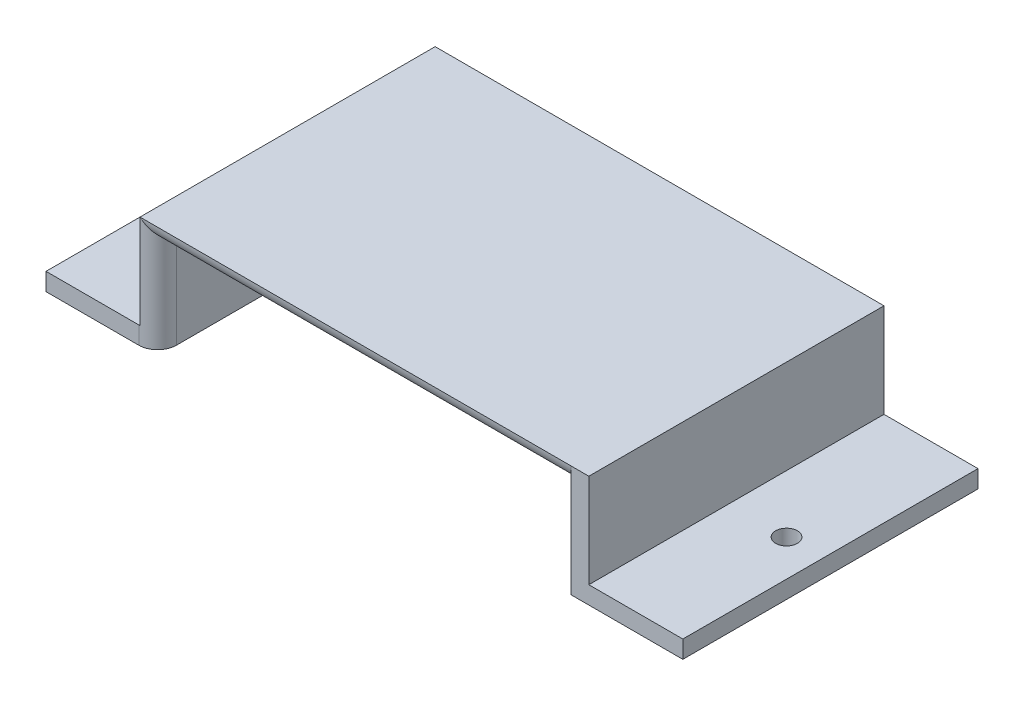
SolidWorks part; units mm, degrees
ref_plane "Front Plane" through (0, 0, 0) normal (0, 0, 1) x (1, 0, 0)
ref_plane "Top Plane" through (0, 0, 0) normal (0, 1, 0) x (1, 0, 0)
ref_plane "Right Plane" through (0, 0, 0) normal (1, 0, 0) x (0, 0, -1)
sketch "Sketch1" plane through (0, 0, 0) normal (0, 0, 1) x (1, 0, 0)
  line L0 (-43.0212, 0) -> (-30.3213, 0)
  line L1 (55, 0) -> (-55, 0) construction
  line L2 (-30.3213, 0) -> (-30.3213, 12.7)
  line L3 (-30.3213, 12.7) -> (30.3213, 12.7)
  line L4 (30.3213, 12.7) -> (30.3213, 0)
  line L5 (30.3213, 0) -> (43.0213, 0)
  line L6 (43.0213, 0) -> (43.0213, -2.3813)
  line L7 (43.0213, -2.3813) -> (27.94, -2.3813)
  line L8 (27.94, -2.3813) -> (27.94, 10.3188)
  line L9 (27.94, 10.3188) -> (-27.94, 10.3187)
  line L10 (-27.94, 10.3187) -> (-27.94, -2.3813)
  line L11 (-27.94, -2.3813) -> (-43.0213, -2.3813)
  line L12 (-43.0213, -2.3813) -> (-43.0212, 0)
  line L13 (0, -55) -> (0, 55) construction
  point P15 (0, 12.7)
  dimension "D1" = 12.7
  dimension "D2" = 55.88
  dimension "D3" = 2.3813
  dimension "D4" = 2.3813
  dimension "D5" = 2.3813
  dimension "D6" = 2.3813
  dimension "D7" = 2.3813
  dimension "D8" = 12.7
  dimension "D9" = 12.7
extrude "Boss-Extrude1" add sketch "Sketch1" along normal blind 39.878 contours L9 L10 L11 L12 L0 L2 L3 L4 L5 L6 L7 L8
hole_wizard "#4 Clearance Hole1" positions "Sketch2" profile "Sketch3" hole size "#4" standard "ANSI Inch" end condition through all
sketch "Sketch2" plane through (0, 0, 0) normal (0, 1, 0) x (1, 0, 0)
  line L4 (-43.0212, -39.878) -> (-43.0212, 0)
  line L6 (-43.0212, -20.9486) -> (-30.3213, -20.9486)
  line L9 (-30.3213, -39.878) -> (-30.3213, 0) construction
  line L10 (-43.0212, -39.878) -> (-30.3213, -39.878)
  line L13 (0, -8.2947) -> (0, 8.2947) construction
  point P0 (-38.1, -20.9486)
  dimension "D1" = 38.1
sketch "Sketch3" plane through (-38.1, 0, 20.9486) normal (1, 0, 0) x (0, 0, 1)
  line L0 (0, 0) -> (0, 2.3813)
  line L1 (0, 2.3813) -> (1.4732, 2.3813)
  line L2 (1.4732, 2.3813) -> (1.4732, 0)
  line L5 (1.4732, 0) -> (0, 0)
  line L11 (0, -6.35) -> (0, 107.95) construction
  dimension "Thru Hole Dia." = 2.9464
  dimension "Thru Hole Depth" = 2.3813
mirror "Mirror1" about plane through (0, 0, 0) normal (1, 0, 0) of "#4 Clearance Hole1"
ref_plane "Plane1" through (0, 0, 19.939) normal (0, 0, 1) x (1, 0, 0)
fillet "Fillet1" radius 2.54 1 edges at (-27.94, 3.9688, 39.878)
fillet "Fillet2" radius 2.54 1 edges at (-1.1906, 10.3188, 39.878)
equation "\"D4@Sketch1\"=\"D3@Sketch1\""
equation "\"D5@Sketch1\"=\"D3@Sketch1\""
equation "\"D6@Sketch1\"=\"D3@Sketch1\""
equation "\"D7@Sketch1\"=\"D3@Sketch1\""
